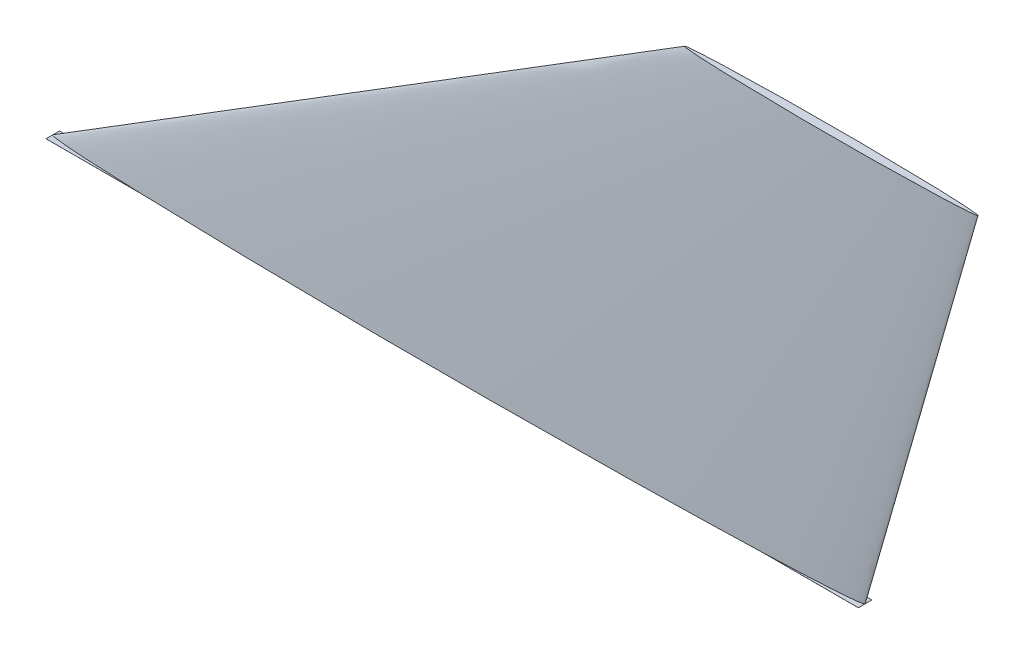
SolidWorks part; units mm, degrees
ref_plane "Front Plane" through (0, 0, 0) normal (0, 0, 1) x (1, 0, 0)
ref_plane "Top Plane" through (0, 0, 0) normal (0, 1, 0) x (1, 0, 0)
ref_plane "Right Plane" through (0, 0, 0) normal (1, 0, 0) x (0, 0, -1)
sketch "Sketch1" plane through (0, 0, 0) normal (0, 0, 1) x (1, 0, 0)
  line L0 (0, 0) -> (140, 87)
  line L1 (140, 87) -> (205, 87)
  line L2 (205, 87) -> (180, 0)
  line L3 (180, 0) -> (180, -0.01)
  line L4 (180, -0.01) -> (0, -0.01)
  line L5 (0, -0.01) -> (0, 0)
  line L6 (0, 0) -> (180, 0)
  dimension "D1" = 180
  dimension "D2" = 65
  dimension "D3" = 0.01
  dimension "D4" = 140
  dimension "D5" = 87
sketch "Sketch2" plane through (0, 0, 0) normal (0, 1, 0) x (1, 0, 0)
  line L0 (0, 0) -> (90, 0) construction
  line L1 (180, 0) -> (0, 0) construction
  line L2 (90, 0) -> (180, 0) construction
  line L3 (140, 0) -> (205, 0) construction
  line L4 (90, 0) -> (90, 2.5) construction
  line L5 (90, 0) -> (90, -2.5) construction
  spline S0 degree 3 poles (90, -3.75) (225, 0) (90, 3.75) (-45, 0) (90, -3.75) (225, 0) (90, 3.75) knots -0.75 -0.5 -0.25 0 0.25 0.5 0.75 1 1.25 1.5 1.75 only from (180, 0) to (180, 0)
  dimension "D2" = 2.5
  dimension "D1" = 180
ref_plane "Plane1" through (0, 87, 0) normal (0, 1, 0) x (1, 0, 0)
sketch "Sketch3" plane through (0, 87, 0) normal (0, 1, 0) x (1, 0, 0)
  line L0 (140, 0) -> (172.5, 0) construction
  line L1 (172.5, 0) -> (205, 0) construction
  line L2 (172.5, 0) -> (172.5, 1) construction
  line L3 (172.5, 0) -> (172.5, -1) construction
  spline S0 degree 3 poles (172.5, -1.5) (123.75, 0) (172.5, 1.5) (221.25, 0) (172.5, -1.5) (123.75, 0) (172.5, 1.5) knots -0.75 -0.5 -0.25 0 0.25 0.5 0.75 1 1.25 1.5 1.75 only from (140, 0) to (140, 0)
  dimension "D1" = 32.5
  dimension "D2" = 1
extrude "Boss-Extrude1" add sketch "Sketch1" along normal mid plane 3 contours L6 L5 L4 L3 region at (90, -0.005, 0)
loft "Loft2" add profiles "Sketch2", "Sketch3" connector at (180, 0, 0) connector at (205, 87, 0)
chamfer "Chamfer1" [suppressed] tangent propagation no
chamfer "Chamfer2" [suppressed] tangent propagation no
